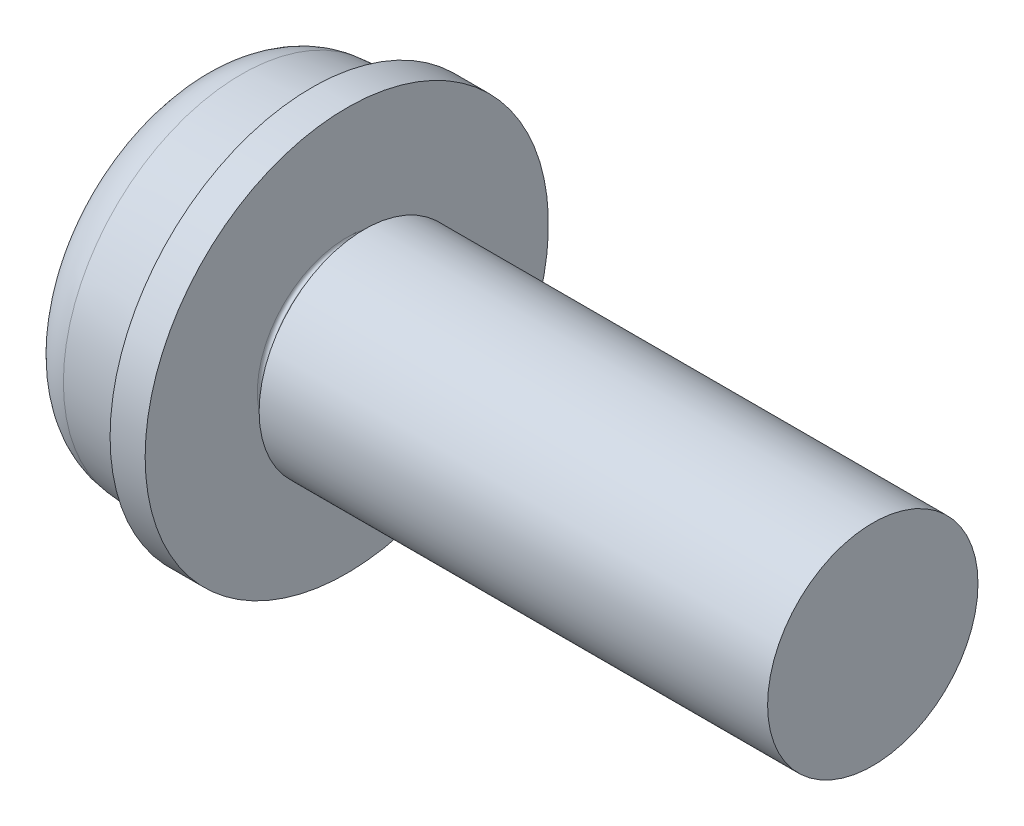
SolidWorks part; units mm, degrees
other "詳細ｱｲﾃﾑ1"
ref_plane "z0" through (0, 0, 0) normal (0, 0, 1) x (1, 0, 0)
ref_plane "y0" through (0, 0, 0) normal (0, 1, 0) x (1, 0, 0)
ref_plane "x0" through (0, 0, 0) normal (1, 0, 0) x (0, 0, -1)
sketch "ｽｹｯﾁ1" plane through (0, 0, 0) normal (0, 0, 1) x (1, 0, 0)
  line L0 (0, 0) -> (30.0467, 0) construction
  line L1 (-3.0071, 5.0744) -> (-1, 5.25)
  line L2 (0, 5.75) -> (0, 2.45)
  line L3 (15, 0) -> (-4.9, 0)
  line L4 (0, 2.45) -> (0.5, 2.45)
  line L5 (0.5, 2.45) -> (0.5, 3)
  line L6 (0.5, 3) -> (15, 3)
  line L7 (15, 3) -> (15, 0)
  line L8 (0, 5.75) -> (-1, 5.75)
  line L9 (-1, 5.75) -> (-1, 5.25)
  arc A0 (-4.3135, 4.0097) -> (-4.9, 0) centre (9.1, 0) ccw
  arc A1 (-4.3135, 4.0097) -> (-3.0071, 5.0744) centre (-2.8763, 3.5801) cw
  point P18 (-3.9808, 4.9892)
  dimension "D10" = 14
  dimension "D12" = 1.5
  dimension "D5" = 0.5
  dimension "D7" = 15
  dimension "D3" = 4.9
  dimension "D1" = 0.9192
  dimension "D4" = 6
  dimension "D8" = 85
  dimension "D6" = 4.9
  dimension "D2" = 11.5
  dimension "D9" = 1
  dimension "D11" = 10.5
revolve "ﾍﾞｰｽ -回転" add sketch "ｽｹｯﾁ1" angle 360 about L0
cosmetic thread "ねじ山1" parameters "D2"=4.9
ref_plane "平面4" through (-4.9, 0, 0) normal (1, 0, 0) x (0, 0, -1)
sketch "ｽｹｯﾁ2" plane through (-4.9, 0, 0) normal (1, 0, 0) x (0, 0, -1)
  line L0 (0.71, -3.15) -> (-0.71, -3.15)
  line L1 (0.71, -3.15) -> (0.71, -1.01)
  line L2 (-0.71, 3.15) -> (0.71, 3.15)
  line L3 (-0.71, 3.15) -> (-0.71, 1.01)
  line L4 (3.15, -0.71) -> (1.01, -0.71)
  line L5 (3.15, -0.71) -> (3.15, 0.71)
  line L6 (-3.15, 0.71) -> (-1.01, 0.71)
  line L7 (-3.15, 0.71) -> (-3.15, -0.71)
  line L8 (3.15, 0) -> (-3.15, 0) construction
  line L9 (0, 3.15) -> (0, -3.15) construction
  line L10 (1.01, 0.71) -> (3.15, 0.71)
  line L11 (-1.01, -0.71) -> (-3.15, -0.71)
  line L12 (0.71, 1.01) -> (0.71, 3.15)
  line L13 (-0.71, -1.01) -> (-0.71, -3.15)
  arc A0 (-1.01, 0.71) -> (-0.71, 1.01) centre (-1.01, 1.01) ccw
  arc A1 (1.01, 0.71) -> (0.71, 1.01) centre (1.01, 1.01) cw
  arc A2 (0.71, -1.01) -> (1.01, -0.71) centre (1.01, -1.01) cw
  arc A3 (-1.01, -0.71) -> (-0.71, -1.01) centre (-1.01, -1.01) cw
  point P21 (0.71, 0.71)
  point P26 (-0.71, -0.71)
  dimension "D3" = 0.3
  dimension "D1" = 1.42
  dimension "D2" = 6.3
extrude "ｶｯﾄ - 押し出し1" cut sketch "ｽｹｯﾁ2" along normal blind 2 draft 8
fillet "ﾌｨﾚｯﾄ1" radius 0.1 1 edges at (0, 0, 2.45)
sketch "ｽｹｯﾁ3" plane through (15, 0, 0) normal (1, 0, 0) x (0, 0, -1)
  circle A0 centre (0, 0) radius 3 construction
  circle A1 centre (0, 0) radius 3
  circle A2 centre (0, 0) radius 2.45
  dimension "D1" = 4.9
extrude "ｶｯﾄ - 押し出し2" [suppressed] cut sketch "ｽｹｯﾁ3" against normal blind 15
sketch "ｽｹｯﾁ4" plane through (0, 0, 0) normal (1, 0, 0) x (0, 0, -1)
  line L1 (0, 5.7735) -> (-5, 2.8868)
  line L2 (-5, 2.8868) -> (-5, -2.8868)
  line L3 (-5, -2.8868) -> (0, -5.7735)
  line L4 (0, -5.7735) -> (5, -2.8868)
  line L5 (5, -2.8868) -> (5, 2.8868)
  line L6 (5, 2.8868) -> (0, 5.7735)
  circle A0 centre (0, 0) radius 5 construction
  dimension "D1" = 10
extrude "ｶｯﾄ - 押し出し3" [suppressed] cut sketch "ｽｹｯﾁ4" against normal through all from offset 1.5 flip side to cut offset against normal yes
equation "\"D1@ｶｯﾄ - 押し出し2\" = \"D7@ｽｹｯﾁ1\""
equation "\"D1@平面4\" = \"D3@ｽｹｯﾁ1\""
